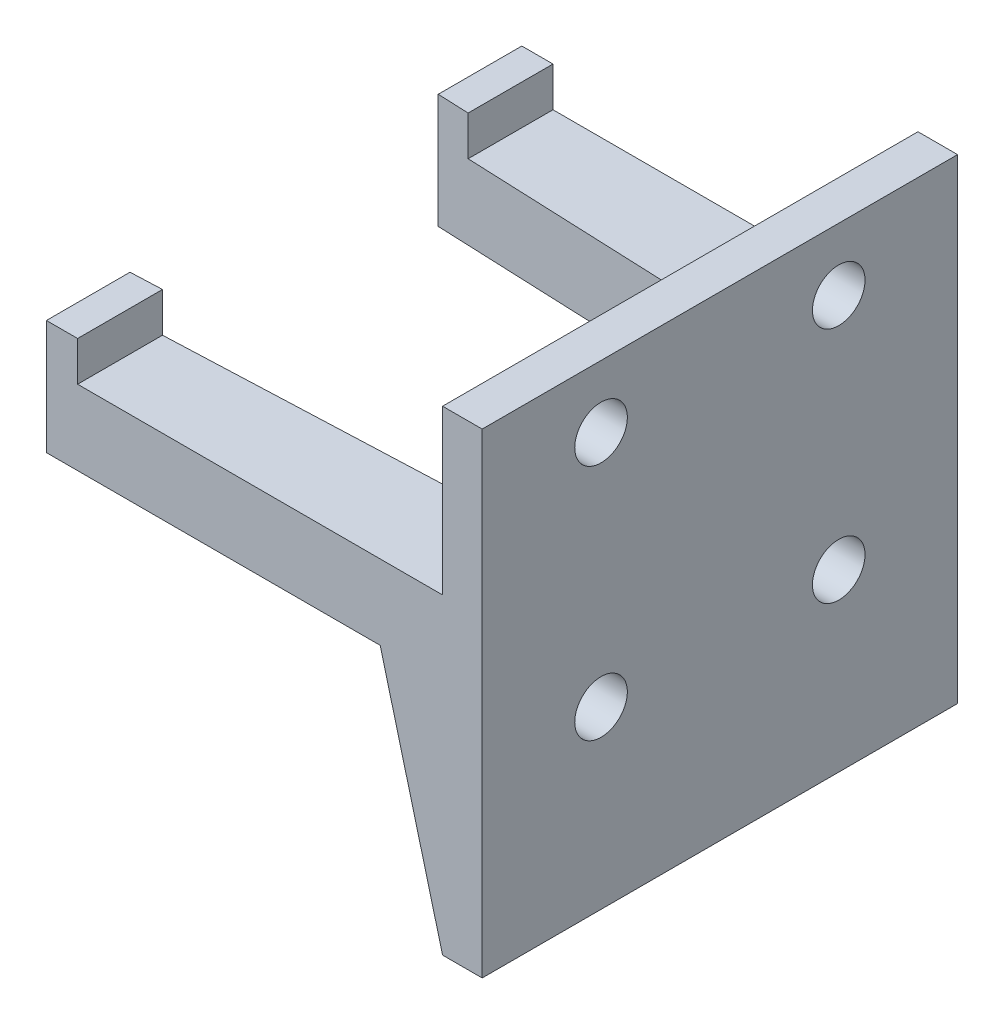
SolidWorks part; units mm, degrees
note: The reader was unsure of these and kept them because the rebuilt part matched: shared geometry of "Sketch3<3>".
ref_plane "Front Plane" through (0, 0, 0) normal (0, 0, 1) x (1, 0, 0)
ref_plane "Top Plane" through (0, 0, 0) normal (0, 1, 0) x (1, 0, 0)
ref_plane "Right Plane" through (0, 0, 0) normal (1, 0, 0) x (0, 0, -1)
sketch "Sketch1" plane through (0, 0, 0) normal (0, 0, 1) x (1, 0, 0)
  line L0 (0, 0) -> (0, -76.2)
  line L1 (0, -26.2) -> (-63.5, -26.2)
  line L2 (-63.5, -26.2) -> (-63.5, -38.2)
  line L3 (-63.5, -38.2) -> (0, -38.2)
  line L4 (-10, -38.2) -> (0, -76.2)
  line L5 (-63.5, -32.2) -> (-13.5, -32.2) construction
  line L6 (-63.5, -26.2) -> (-63.5, -19.85)
  line L7 (0, 0) -> (6.35, 0)
  line L8 (6.35, 0) -> (6.35, -76.2)
  line L9 (6.35, -76.2) -> (0, -76.2)
  line L10 (-63.5, -19.85) -> (-58.5, -19.85)
  line L11 (-58.5, -19.85) -> (-58.5, -26.2)
  dimension "D1" = 63.5
  dimension "D2" = 12
  dimension "D3" = 76.2
  dimension "D4" = 10
  dimension "D5" = 6.35
  dimension "D6" = 50
  dimension "D7" = 50
  dimension "D8" = 5
  dimension "D9" = 6.35
extrude "Boss-Extrude1" add sketch "Sketch1" along normal blind 76.2
sketch "Sketch2" plane through (0, 0, 0) normal (0, 1, 0) x (1, 0, 0)
  line L0 (0, -16.129) -> (0, -16.029)
  line L1 (-70, -60.071) -> (0, -60.071)
  line L2 (-70, -60.071) -> (-70, -16.129)
  line L3 (-70, -16.129) -> (0, -16.129)
  line L4 (0, -60.071) -> (0, -16.129)
  line L5 (0, -76.2) -> (0, 0) construction
  line L6 (-70, -13.129) -> (-70, -16.129)
  line L7 (-70, -60.071) -> (-70, -63.071)
  line L8 (0, 0) -> (-58.5, 0) construction
  line L9 (0, -60.071) -> (0, -60.171)
  line L10 (0, -76.2) -> (0, 0) construction
  line L11 (0, -16.029) -> (-70, -13.129)
  line L12 (0, -60.171) -> (-70, -63.071)
  dimension "D1" = 43.942
  dimension "D2" = 70
  dimension "D3" = 16.129
  dimension "D4" = 0
  dimension "D5" = 3
  dimension "D6" = 0.1
  dimension "D7" = 0.1
extrude "Cut-Extrude1" cut sketch "Sketch2" against normal up to surface (76.2 mm away) contours L0 L11 L6 L3 | L1 L4 L3 L2 | L12 L9 L1 L7 up to face at (3.175, -76.2, 38.1)
sketch "Sketch3" plane through (0, 0, 0) normal (1, 0, 0) x (0, 0, -1)
  line L2 (0, 0) -> (0, -76.2) construction
  line L3 (-76.2, 0) -> (0, 0) construction
  circle A0 centre (-57.15, -10) radius 4.2164
  circle A1 centre (-19.05, -10) radius 4.2164
  circle A2 centre (-19.05, -48.1) radius 4.2164
  circle A3 centre (-57.15, -48.1) radius 4.2164
  circle A4 centre (-57.15, -48.1) radius 8.89
  circle A5 centre (-19.05, -48.1) radius 8.89
  dimension "D6" = 8.4328
  dimension "D1" = 17.78
  dimension "D2" = 38.1
  dimension "D3" = 19.05
  dimension "D4" = 38.1
  dimension "D5" = 10
extrude "Cut-Extrude2" cut sketch "Sketch3" along direction (1, 0, 0) on the side of the normal up to surface (6.35 mm away) and the other way up to surface (58.5 mm away) contours A1 | A0 | A3 | A2
extrude "Cut-Extrude3" cut sketch "Sketch3<3>" against normal blind 10 contours A5 A2 | A4 A3
sketch "Sketch3<3>" plane through (0, 0, 0) normal (1, 0, 0) x (0, 0, -1) same geometry as "Sketch3"
equation "\"width\"= 3in"
equation "\"D1@Boss-Extrude1\"=\"width\""
equation "\"D7@Sketch2\"=\"D6@Sketch2\""
